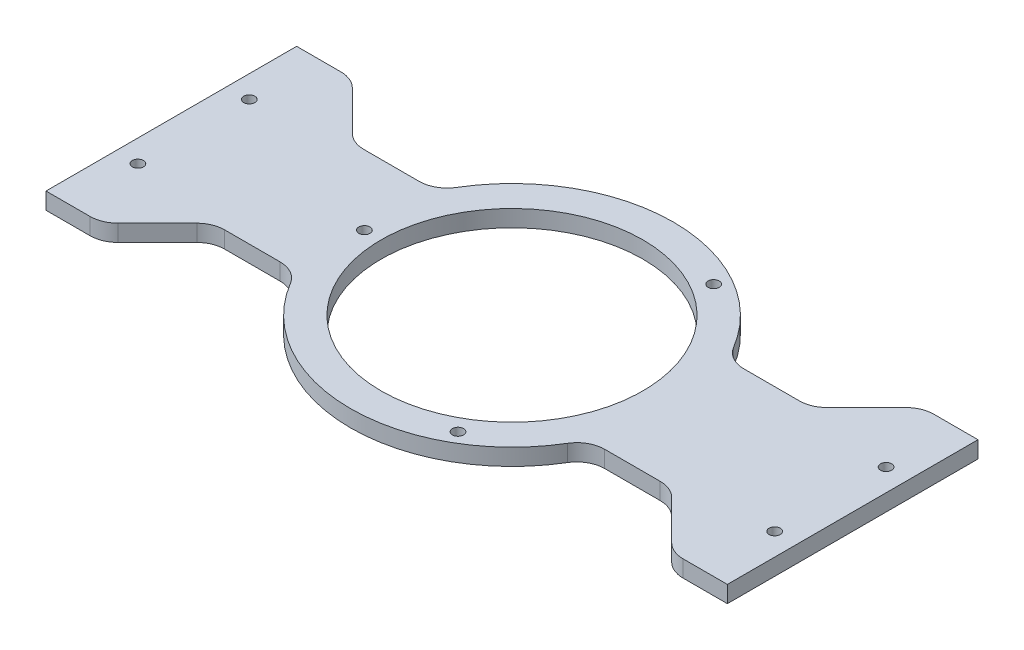
SolidWorks part; units mm, degrees
ref_plane "Front Plane" through (0, 0, 0) normal (0, 0, 1) x (1, 0, 0)
ref_plane "Top Plane" through (0, 0, 0) normal (0, 1, 0) x (1, 0, 0)
ref_plane "Right Plane" through (0, 0, 0) normal (1, 0, 0) x (0, 0, -1)
sketch "Sketch2" plane through (0, 0, 0) normal (0, 1, 0) x (1, 0, 0)
  line L0 (26.1677, 12.5) -> (41.1677, 12.5)
  line L1 (26.1677, -12.5) -> (41.1677, -12.5)
  line L2 (41.1677, 12.5) -> (51.1677, 22.5)
  line L3 (51.1677, 22.5) -> (61.1677, 22.5)
  line L4 (61.1677, 22.5) -> (61.1677, -22.5)
  line L5 (61.1677, -22.5) -> (51.1677, -22.5)
  line L6 (51.1677, -22.5) -> (41.1677, -12.5)
  line L7 (-55, 0) -> (55, 0) construction
  circle A0 centre (0, 0) radius 23 construction
  circle A2 centre (0, 0) radius 23.5
  circle A3 centre (57.1677, 10) radius 1
  circle A4 centre (57.1677, -10) radius 1
  circle A5 centre (0, 0) radius 29
  point P13 (61.1677, 0)
  dimension "D1" = 46
  dimension "D12" = 2
  dimension "D3" = 58
  dimension "D2" = 0.5
  dimension "D4" = 25
  dimension "D5" = 15
  dimension "D6" = 45
  dimension "D7" = 10
  dimension "D8" = 45
  dimension "D9" = 45
  dimension "D10" = 4
  dimension "D11" = 10
extrude "Boss-Extrude1" add sketch "Sketch2" along normal blind 3 contours A5 A2 region at (27.4831, 0, -6.2272)
extrude "Boss-Extrude2" add sketch "Sketch2<3>" along normal up to surface (3 mm away) contours A5 L1 L6 L5 L4 L3 L2 L0 A4 A3 region at (46.8898, 0, 0) up to face at (0, 3, 23.5)
sketch "Sketch2<3>" plane through (0, 0, 0) normal (0, 1, 0) x (1, 0, 0) same geometry as "Sketch2"
fillet "Fillet1" radius 5 6 edges at (26.1677, 1.5, -12.5) (26.1677, 1.5, 12.5) (51.1677, 1.5, 22.5) (51.1677, 1.5, -22.5) (41.1677, 1.5, -12.5) (41.1677, 1.5, 12.5)
sketch "Sketch3" plane through (0, 3, 0) normal (0, 1, 0) x (1, 0, 0)
  line L0 (0, 0) -> (13.25, 22.9497) construction
  circle A0 centre (13.25, 22.9497) radius 1
  dimension "D3" = 2
  dimension "D1" = 26.5
  dimension "D2" = 60
extrude "Cut-Extrude1" cut sketch "Sketch3" against normal up to surface (3 mm away) contours A0 up to face at (0, 0, 23.5)
pattern_circular "CirPattern1" count 3 over 360 about axis through (0, 3, 0) along (0, 1, 0) of "Cut-Extrude1"
mirror "Mirror1" about plane through (0, 0, 0) normal (1, 0, 0) of "Fillet1", "Boss-Extrude2"
equation "\"motor-dia\" = 46"
equation "\"motor-holes-rad\" = 15"
equation "\"motor-height\" = 21"
equation "\"motor-case-thickness\" = 2"
equation "\"D1@Sketch2\"=\"motor-dia\""
